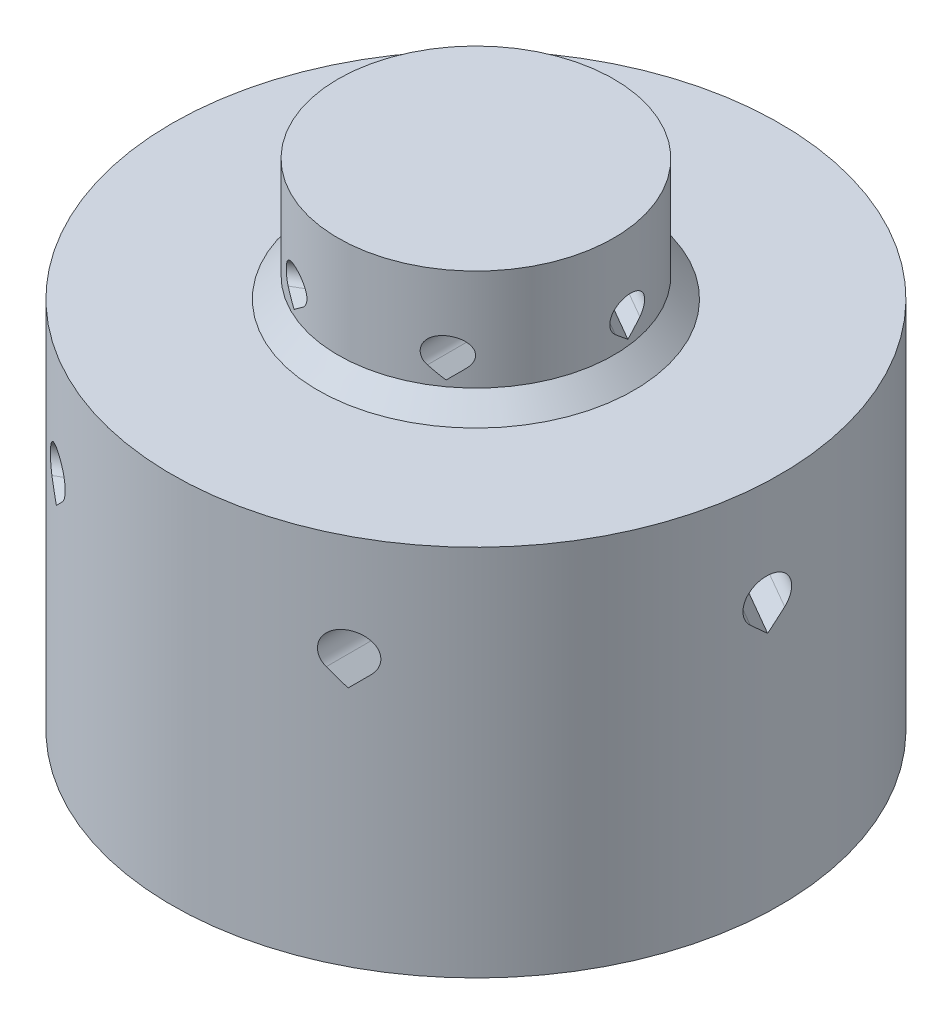
SolidWorks part; units mm, degrees
material "ASTM A36 Steel"
ref_plane "Front Plane" through (0, 0, 0) normal (0, 0, 1) x (1, 0, 0)
ref_plane "Top Plane" through (0, 0, 0) normal (0, 1, 0) x (1, 0, 0)
ref_plane "Right Plane" through (0, 0, 0) normal (1, 0, 0) x (0, 0, -1)
ref_axis "Axis1" through (0, 42.935, 0) along (0, -1, 0)
sketch "Sketch1" plane through (0, 0, 0) normal (0, 0, 1) x (1, 0, 0)
  line L1 (-5.3975, 0) -> (-5.3975, -3.9688)
  line L2 (-6.1912, -4.7625) -> (-11.9062, -4.7625)
  line L3 (-11.9062, -4.7625) -> (-11.9062, -7.1755)
  line L7 (-3.81, -1.5875) -> (-3.81, -13.0175)
  line L8 (-3.81, -13.0175) -> (-2.54, -14.2875)
  line L9 (-2.54, -14.2875) -> (-2.54, -16.8275)
  line L10 (-2.54, -16.8275) -> (-3.3337, -16.8275)
  line L11 (-3.3337, -16.8275) -> (-3.3337, -14.6163)
  line L12 (-3.3337, -14.6163) -> (-4.6037, -13.3463)
  line L13 (-4.6037, -13.3463) -> (-4.6037, -7.9375)
  line L14 (0, -1.5875) -> (0, -17.8202) construction
  line L15 (-4.6037, -7.9375) -> (-6.35, -7.9375)
  line L16 (-6.35, -7.9375) -> (-6.35, -7.1755)
  line L17 (-6.35, -7.1755) -> (-11.9062, -7.1755)
  line L19 (-5.3975, 0) -> (-4.445, 0)
  line L20 (-4.445, 0) -> (-4.445, -1.5875)
  line L21 (-4.445, -1.5875) -> (-3.81, -1.5875)
  line L22 (-6.1912, -4.7625) -> (-5.3975, -3.9688)
  point P10 (-6.35, -7.5565)
  dimension "D1" = 3.81
  dimension "D2" = 2.54
  dimension "D3" = 135
  dimension "D4" = 11.43
  dimension "D5" = 2.54
  dimension "D6" = 1.5875
  dimension "D7" = 3.175
  dimension "D8" = 0.7937
  dimension "D9" = 0.7937
  dimension "D10" = 0.762
  dimension "D11" = 1.5875
  dimension "D12" = 11.9062
  dimension "D13" = 3.175
  dimension "D14" = 135
  dimension "D15" = 6.35
  dimension "D16" = 4.445
  dimension "D17" = 0.7937
  dimension "D18" = 0.7937
revolve "Revolve1" add sketch "Sketch1" angle 360 about L14
sketch "Sketch2" plane through (0, 0, 0) normal (0, 0, 1) x (1, 0, 0)
  line L0 (-6.35, -7.9375) -> (-6.35, -14.2875)
  line L1 (-6.35, -7.1755) -> (-11.9062, -7.1755) construction
  line L2 (-6.35, -14.2875) -> (-4.445, -16.1925)
  line L3 (-4.445, -16.1925) -> (-4.445, -22.5425)
  line L4 (-4.445, -22.5425) -> (-6.35, -22.5425)
  line L5 (-6.35, -22.5425) -> (-6.35, -19.3675)
  line L7 (-11.9062, -7.1755) -> (-11.9062, -19.3675)
  line L8 (-10.3886, -19.3675) -> (-11.9062, -19.3675)
  line L9 (0, 42.935) -> (0, -67.065) construction
  line L10 (-6.35, -7.9375) -> (-6.35, -7.1755)
  line L11 (-6.35, -7.1755) -> (-11.9062, -7.1755)
  line L13 (0, -1.5875) -> (0, -17.8202) construction
  line L14 (-6.35, -19.3675) -> (-7.3152, -19.3675)
  line L15 (-7.3152, -19.3675) -> (-7.3152, -17.3863)
  line L16 (-7.3152, -17.3863) -> (-10.3886, -17.3863)
  line L17 (-10.3886, -17.3863) -> (-10.3886, -19.3675)
  point P2 (-11.8448, -7.1755)
  point P18 (-11.9062, -7.1755)
  dimension "D1" = 4.445
  dimension "D2" = 3.175
  dimension "D3" = 135
  dimension "D4" = 6.35
  dimension "D5" = 6.35
  dimension "D6" = 6.35
  dimension "D7" = 3.0734
  dimension "D8" = 1.9812
  dimension "D9" = 10.3886
revolve "Revolve2" add sketch "Sketch2" angle 360 about L14
sketch "Sketch3" plane through (0, 0, 0) normal (0, 0, 1) x (1, 0, 0)
  line L0 (-4.445, -1.5875) -> (0, -1.5875)
  line L1 (4.445, -1.5875) -> (-4.445, -1.5875) construction
  line L2 (0, -1.5875) -> (0, 0)
  line L3 (0, 0) -> (-4.445, 0)
  line L4 (-4.445, 0) -> (-4.445, -1.5875)
revolve "Revolve3" add sketch "Sketch3" angle 360 about L2
sketch "Sketch8" plane through (0, 0, 0) normal (0, 0, 1) x (1, 0, 0)
  line L0 (-3.1877, -3.7376) -> (-3.6277, -3.2975)
  line L1 (-2.7477, -3.2975) -> (-3.1877, -3.7376)
  line L2 (-3.1877, -2.8575) -> (-3.1877, -3.7376) construction
  line L3 (-3.81, -1.5875) -> (-3.81, -13.0175) construction
  line L4 (5.3975, 0) -> (-5.3975, 0) construction
  arc A0 (-3.6277, -3.2975) -> (-2.7477, -3.2975) centre (-3.1877, -2.8575) cw
  point P4 (-3.5416, -4.5666)
  point P5 (-3.81, -2.8575)
  point P6 (0, 0)
  point P7 (0, 0)
  dimension "D2" = 0.6223
  dimension "D1" = 90
  dimension "D3" = 2.8575
extrude "Cut-Extrude1" cut sketch "Sketch8" against normal through all
pattern_circular "CirPattern1" count 6 over 360 about axis through (0, 42.935, 0) along (0, -1, 0) of "Cut-Extrude1"
sketch "Sketch9" plane through (0, 0, 0) normal (0, 0, 1) x (1, 0, 0)
  line L0 (-5.5372, -9.9125) -> (-6.1119, -9.3377)
  line L1 (-4.9625, -9.3377) -> (-5.5372, -9.9125)
  line L2 (-5.5372, -9.9125) -> (-5.5372, -8.763) construction
  line L3 (-6.35, -7.9375) -> (-6.35, -14.2875) construction
  line L5 (-6.35, -7.1755) -> (-11.9062, -7.1755) construction
  arc A0 (-6.1119, -9.3377) -> (-4.9625, -9.3377) centre (-5.5372, -8.763) cw
  point P4 (-6.35, -8.763)
  point P5 (0, 0)
  dimension "D2" = 0.8128
  dimension "D1" = 90
  dimension "D3" = 1.5875
extrude "Cut-Extrude2" cut sketch "Sketch9" against normal through all
pattern_circular "CirPattern2" count 6 over 360 about axis through (0, 42.935, 0) along (0, -1, 0) of "Cut-Extrude2"
ref_axis "Axis2" through (13.97, 0, 0) along (-1, 0, 0)
ref_axis "Axis3" through (0, 0, -13.97) along (0, 0, 1)
equation "\".o625\"=0.0585896"
